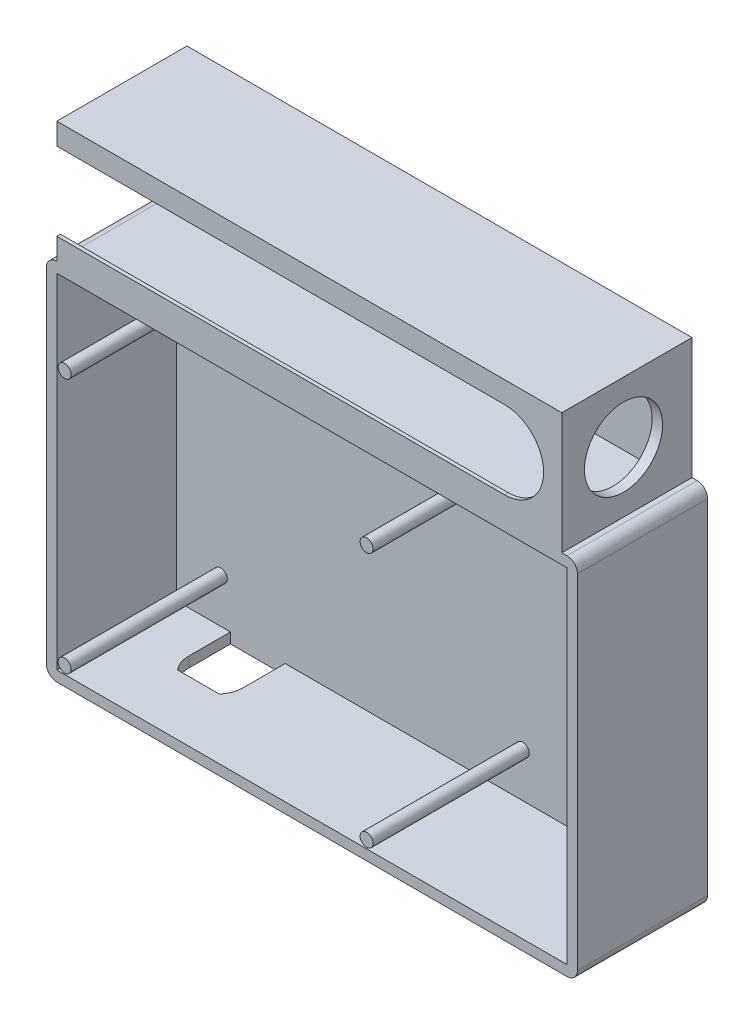
SolidWorks part; units mm, degrees
ref_plane "Front Plane" through (0, 0, 0) normal (0, 0, 1) x (1, 0, 0)
ref_plane "Top Plane" through (0, 0, 0) normal (0, 1, 0) x (1, 0, 0)
ref_plane "Right Plane" through (0, 0, 0) normal (1, 0, 0) x (0, 0, -1)
sketch "Sketch1" plane through (0, 0, 0) normal (0, 0, 1) x (1, 0, 0)
  line L0 (-5, -5) -> (93, -5)
  line L1 (0, 0) -> (85, 0)
  line L2 (0, 0) -> (0, 56)
  line L3 (0, 56) -> (85, 56)
  line L4 (85, 0) -> (85, 56)
  line L5 (3.5, 56) -> (3.5, 52.5)
  line L6 (-5, -5) -> (-5, 61)
  line L7 (-5, 61) -> (93, 61)
  line L8 (93, 0) -> (93, 56)
  line L9 (93, -5) -> (93, 0)
  line L10 (93, 56) -> (93, 61)
  line L11 (-5, 61) -> (85, 61) construction
  line L12 (-5, -5) -> (85, -5) construction
  circle A0 centre (3.5, 52.5) radius 1.25
  circle A1 centre (61.5, 52.5) radius 1.25
  circle A2 centre (61.5, 3.5) radius 1.25
  circle A3 centre (3.5, 3.5) radius 1.25
  dimension "D1" = 2
  dimension "D3" = 5
  dimension "D4" = 8
  dimension "D2" = 2
extrude "Boss-Extrude1" add sketch "Sketch1" along normal blind 2 contours L8 L10 L7 L6 L0 L9 L4 L1 L2 L3 | A0 L3 L2 L1 L4 A3 A2 A1 region at (-3.8185, 28, 0) region at (42.5414, 28, 0)
extrude "Boss-Extrude2" add sketch "Sketch1<3>" along normal blind 32 contours A0 | A3 | A2 | A1 region at (4.3589, 53.3589, 0) region at (61.5, 52.5, 0) region at (61.5, 3.5, 0) region at (3.5, 3.5, 0)
sketch "Sketch1<3>" plane through (0, 0, 0) normal (0, 0, 1) x (1, 0, 0) same geometry as "Sketch1"
sketch "Sketch2" plane through (0, 0, 0) normal (0, 0, -1) x (-1, 0, 0)
  line L0 (7, -5) -> (7, 61)
  line L1 (5, -5) -> (-93, -5)
  line L2 (5, -5) -> (5, 61)
  line L3 (5, 61) -> (-93, 61)
  line L4 (-93, -5) -> (-93, 61)
  line L5 (5, 63) -> (-93, 63)
  line L6 (-95, -5) -> (-95, 61)
  line L7 (5, -7) -> (-93, -7)
  line L8 (7, -7) -> (7, 63) construction
  line L9 (7, 63) -> (-95, 63) construction
  line L10 (-95, -7) -> (-95, 63) construction
  line L11 (7, -7) -> (-95, -7) construction
  arc A0 (7, 61) -> (5, 63) centre (5, 61) ccw
  arc A1 (-93, 63) -> (-95, 61) centre (-93, 61) ccw
  arc A2 (-95, -5) -> (-93, -7) centre (-93, -5) ccw
  arc A3 (7, -5) -> (5, -7) centre (5, -5) cw
  dimension "D2" = 2
  dimension "D1" = 2
extrude "Boss-Extrude3" add sketch "Sketch2" against normal blind 25
sketch "Sketch3" plane through (0, -7, 0) normal (0, -1, 0) x (1, 0, 0)
  line L0 (-7, 0) -> (-7, 10)
  line L1 (-7, 25) -> (-7, 0) construction
  line L2 (-7, 10) -> (5.35, 10)
  line L3 (5.35, 10) -> (5.35, 2)
  line L4 (6.5997, 13.4) -> (14.6003, 13.4)
  line L6 (15.85, 10) -> (15.85, 2)
  line L10 (15.85, 2) -> (5.35, 2)
  arc A0 (6.5997, 13.4) -> (5.35, 10) centre (10.6, 10) ccw
  arc A1 (15.85, 10) -> (14.6003, 13.4) centre (10.6, 10) ccw
extrude "Cut-Extrude1" cut sketch "Sketch3" against normal blind 25 contours L6 A1 L4 A0 L3 L10 region at (10.6, -7, 7.5883)
sketch "Sketch4" plane through (-5, 0, 0) normal (1, 0, 0) x (0, 0, -1)
  line L0 (0, 63) -> (-2, 63)
  line L1 (-25, 63) -> (0, 63) construction
  line L2 (-2, 63) -> (-2, 84.3)
  line L3 (-2, 84.3) -> (-24, 84.3)
  line L4 (0, 63) -> (0, 86.3)
  line L5 (0, 86.3) -> (-24, 86.3)
  line L6 (-24, 84.3) -> (-24, 86.3)
  dimension "D1" = 2
extrude "Boss-Extrude4" add sketch "Sketch4" along normal blind 95 contours L6 L3 L2 L0 L4 L5 region at (-5, 63.3345, 1)
sketch "Sketch5" plane through (90, 0, 0) normal (1, 0, 0) x (0, 0, -1)
  line L1 (0, 63) -> (-24, 63)
  line L2 (0, 63) -> (0, 86.3)
  line L3 (0, 86.3) -> (-24, 86.3)
  line L4 (-24, 63) -> (-24, 86.3)
extrude "Boss-Extrude5" add sketch "Sketch5" along normal blind 2
sketch "Sketch6" plane through (0, 0, 24) normal (0, 0, 1) x (1, 0, 0)
  line L0 (-5, 84.3) -> (-5, 86.3) construction
  line L1 (90, 84.3) -> (-5, 84.3) construction
  line L2 (92, 63) -> (90, 63) construction
  line L3 (90, 84.3) -> (90, 63) construction
  line L4 (92, 86.3) -> (-5, 86.3) construction
  line L5 (92, 86.3) -> (92, 63) construction
  line L6 (-5, 84.3) -> (-5, 86.3)
  line L7 (90, 84.3) -> (-5, 84.3)
  line L8 (92, 63) -> (90, 63)
  line L9 (90, 84.3) -> (90, 63)
  line L10 (92, 86.3) -> (-5, 86.3)
  line L11 (92, 86.3) -> (92, 63)
extrude "Boss-Extrude6" add sketch "Sketch6" along normal blind 0.3
ref_plane "Plane1" through (-5, 84.3, 24.3) normal (0, 0, 1) x (1, 0, 0)
sketch "Sketch7" plane through (-5, 84.3, 24.3) normal (0, 0, 1) x (1, 0, 0)
  line L0 (97, -9.65) -> (86, -9.65)
  line L1 (97, -21.3) -> (0, -21.3)
  line L2 (97, -21.3) -> (97, 2)
  line L3 (97, 2) -> (0, 2)
  line L4 (0, -21.3) -> (0, 2)
  line L5 (86, -17.15) -> (0, -17.15)
  line L6 (86, -2.15) -> (0, -2.15)
  line L7 (0, -2.15) -> (0, -17.15)
  arc A0 (86, -17.15) -> (86, -2.15) centre (86, -9.65) ccw
extrude "Boss-Extrude7" add sketch "Sketch7" along normal up to surface (0.7 mm away) contours A0 L5 L4 L1 L2 L0 | A0 L0 L2 L3 L4 L6 region at (47.4698, 65.5245, 24.3) region at (47.4698, 83.7755, 24.3) up to face at (44, 28, 25)
sketch "Sketch8" plane through (92, 0, 0) normal (1, 0, 0) x (0, 0, -1)
  line L0 (-26.3, 63) -> (0, 86.3)
  circle A0 centre (-13.15, 74.65) radius 7.5
extrude "Cut-Extrude2" cut sketch "Sketch8" against normal blind 2 contours L0 A0 | L0 A0 region at (92, 77.0326, 15.2608) region at (92, 72.2674, 11.0392)
